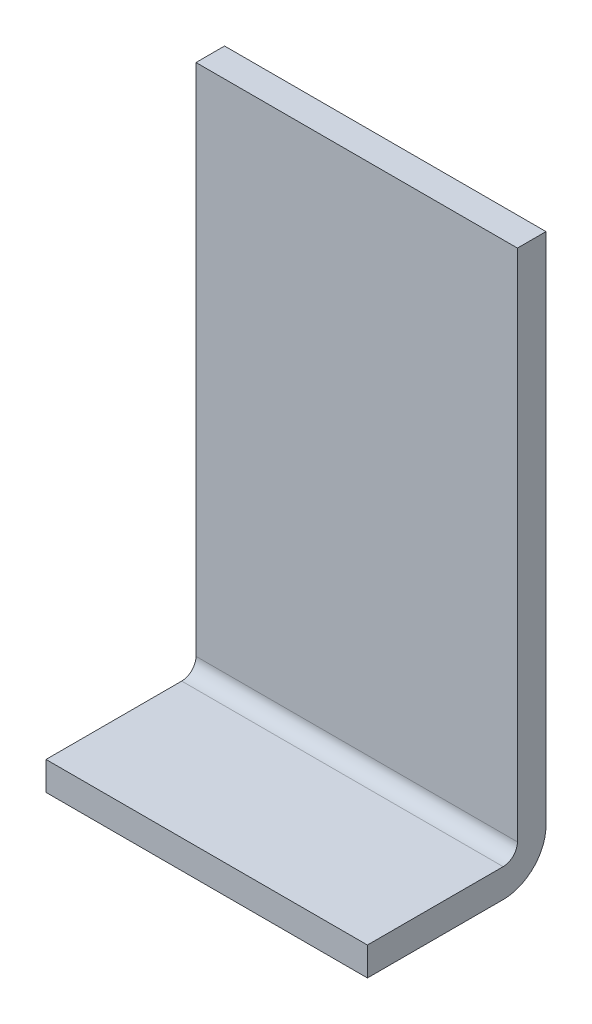
SolidWorks part; units mm, degrees
ref_plane "Front Plane" through (0, 0, 0) normal (0, 0, 1) x (1, 0, 0)
ref_plane "Top Plane" through (0, 0, 0) normal (0, 1, 0) x (1, 0, 0)
ref_plane "Right Plane" through (0, 0, 0) normal (1, 0, 0) x (0, 0, -1)
sketch "Sketch1" plane through (0, 0, 0) normal (0, 1, 0) x (1, 0, 0)
  line L1 (0, 0) -> (22.5, 0)
  line L2 (0, 0) -> (0, 12.5)
  line L3 (0, 12.5) -> (22.5, 12.5)
  line L4 (22.5, 0) -> (22.5, 12.5)
  dimension "D1" = 12.5
  dimension "D2" = 22.5
extrude "Boss-Extrude1" add sketch "Sketch1" along normal blind 2
sketch "Sketch2" plane through (0, 0, -12.5) normal (0, 0, -1) x (-1, 0, 0)
  line L1 (-22.5, 2) -> (0, 2)
  line L2 (-22.5, 2) -> (-22.5, 39)
  line L3 (-22.5, 39) -> (0, 39)
  line L4 (0, 2) -> (0, 39)
  dimension "D1" = 37
extrude "Boss-Extrude2" add sketch "Sketch2" against normal blind 2
fillet "Fillet1" radius 1 1 edges at (11.25, 2, -10.5)
fillet "Fillet2" radius 3 1 edges at (11.25, 0, -12.5)
